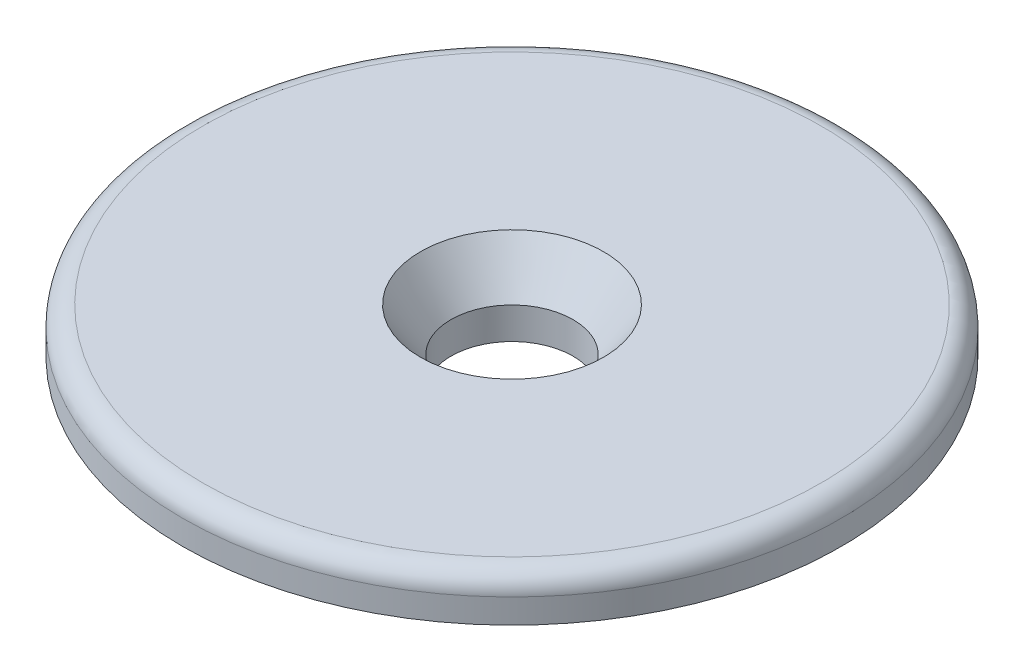
SolidWorks part; units mm, degrees
ref_plane "Alzado" through (0, 0, 0) normal (0, 0, 1) x (1, 0, 0)
ref_plane "Planta" through (0, 0, 0) normal (0, 1, 0) x (1, 0, 0)
ref_plane "Vista lateral" through (0, 0, 0) normal (1, 0, 0) x (0, 0, -1)
sketch "Croquis1" plane through (0, 0, 0) normal (0, 1, 0) x (1, 0, 0)
  circle A0 centre (0, 0) radius 16.2
  circle A1 centre (0, 0) radius 3
  dimension "D1" = 32.4
  dimension "D2" = 6
extrude "Saliente-Extruir1" add sketch "Croquis1" along normal blind 2.2
sketch "Croquis2" plane through (0, 0, 0) normal (0, -1, 0) x (1, 0, 0)
  circle A0 centre (0, 0) radius 3
  circle A1 centre (0, 0) radius 13.5
  circle A2 centre (0, 0) radius 3 construction
  dimension "D1" = 27
extrude "Saliente-Extruir2" add sketch "Croquis2" along normal blind 1.5
fillet "Redondeo1" radius 1 1 edges at (0, 2.2, 16.2)
chamfer "Chaflán1" distance 1.5 angle 55 1 edges at (0, 2.2, 3) first distance on face at (0, 2.2, 15.2)
